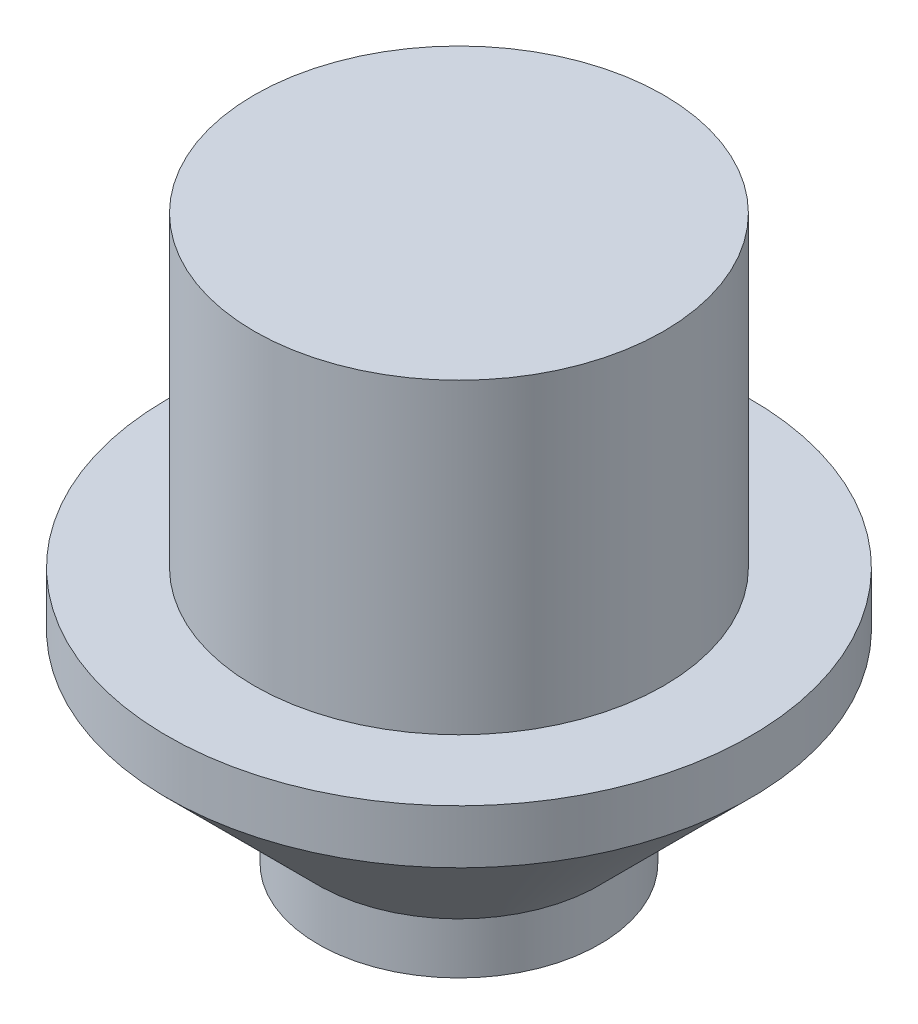
SolidWorks part; units mm, degrees
ref_plane "Front Plane" through (0, 0, 0) normal (0, 0, 1) x (1, 0, 0)
ref_plane "Top Plane" through (0, 0, 0) normal (0, 1, 0) x (1, 0, 0)
ref_plane "Right Plane" through (0, 0, 0) normal (1, 0, 0) x (0, 0, -1)
sketch "Sketch1" plane through (0, 0, 0) normal (0, 0, 1) x (1, 0, 0)
  line L0 (0, 0) -> (1.375, 0)
  line L1 (1.375, 0) -> (1.375, 2)
  line L2 (1.375, 2) -> (2.85, 2)
  line L3 (2.85, 2) -> (2.85, 2.5)
  line L4 (2.85, 2.5) -> (2, 2.5)
  line L5 (2, 2.5) -> (2, 5.5)
  line L6 (2, 5.5) -> (0, 5.5)
  line L7 (0, 5.5) -> (0, 0) construction
  line L8 (0, 0) -> (0, 5.5)
  dimension "D1" = 1.375
  dimension "D2" = 2
  dimension "D3" = 0.5
  dimension "D4" = 3
  dimension "D5" = 2
  dimension "D6" = 0.85
revolve "Revolve1" add sketch "Sketch1" angle 360 about L7
chamfer "Chamfer1" distance 1.5 angle 45 1 edges at (-1.375, 2, 0)
